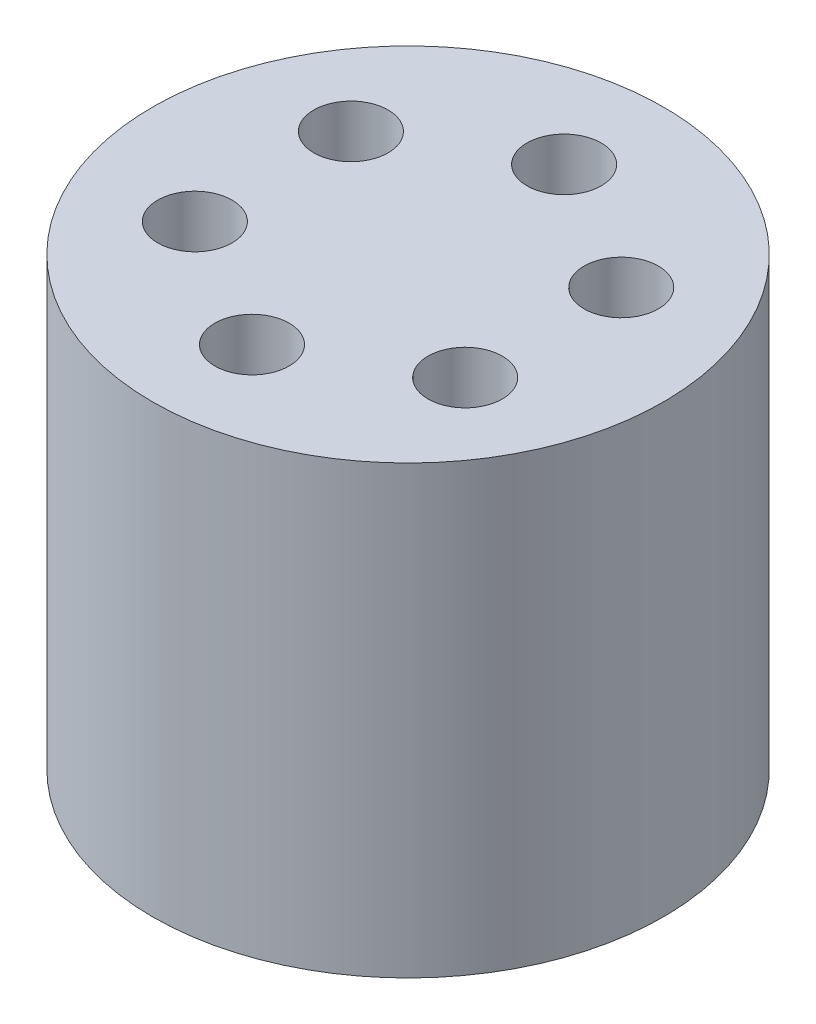
SolidWorks part; units mm, degrees
ref_plane "Front Plane" through (0, 0, 0) normal (0, 0, 1) x (1, 0, 0)
ref_plane "Top Plane" through (0, 0, 0) normal (0, 1, 0) x (1, 0, 0)
ref_plane "Right Plane" through (0, 0, 0) normal (1, 0, 0) x (0, 0, -1)
sketch "Sketch1" plane through (0, 0, 0) normal (0, 1, 0) x (1, 0, 0)
  circle A0 centre (0, 0) radius 18.9
extrude "Boss-Extrude1" add sketch "Sketch1" along normal blind 33
sketch "Sketch2" plane through (0, 33, 0) normal (0, 1, 0) x (1, 0, 0)
  line L1 (0, 11.547) -> (-10, 5.7735)
  line L2 (-10, 5.7735) -> (-10, -5.7735)
  line L3 (-10, -5.7735) -> (0, -11.547)
  line L4 (0, -11.547) -> (10, -5.7735)
  line L5 (10, -5.7735) -> (10, 5.7735)
  line L6 (10, 5.7735) -> (0, 11.547)
  circle A0 centre (0, 0) radius 10 construction
  circle A1 centre (0, 11.547) radius 2.75
  circle A2 centre (10, 5.7735) radius 2.75
  circle A3 centre (10, -5.7735) radius 2.75
  circle A4 centre (0, -11.547) radius 2.75
  circle A5 centre (-10, -5.7735) radius 2.75
  circle A6 centre (-10, 5.7735) radius 2.75
extrude "Cut-Extrude1" cut sketch "Sketch2" against normal blind 25.4 contours L1 A6 L2 | L2 A6 L1 | L6 A1 L1 | L1 A1 L6 | L5 A2 L6 | L6 A2 L5 | L4 A3 L5 | L5 A3 L4 | L3 A4 L4 | L4 A4 L3 | L2 A5 L3 | L3 A5 L2 region at (0, 33, -10.0309) region at (0, 33, -12.3051) region at (-8.687, 33, -5.0154) region at (-10.6565, 33, -6.1525) region at (10.6565, 33, -6.1525) region at (8.687, 33, -5.0154) region at (-8.687, 33, 5.0154) region at (-10.6565, 33, 6.1525) region at (10.6565, 33, 6.1525) region at (8.687, 33, 5.0154) region at (0, 33, 10.0309) region at (0, 33, 12.3051)
